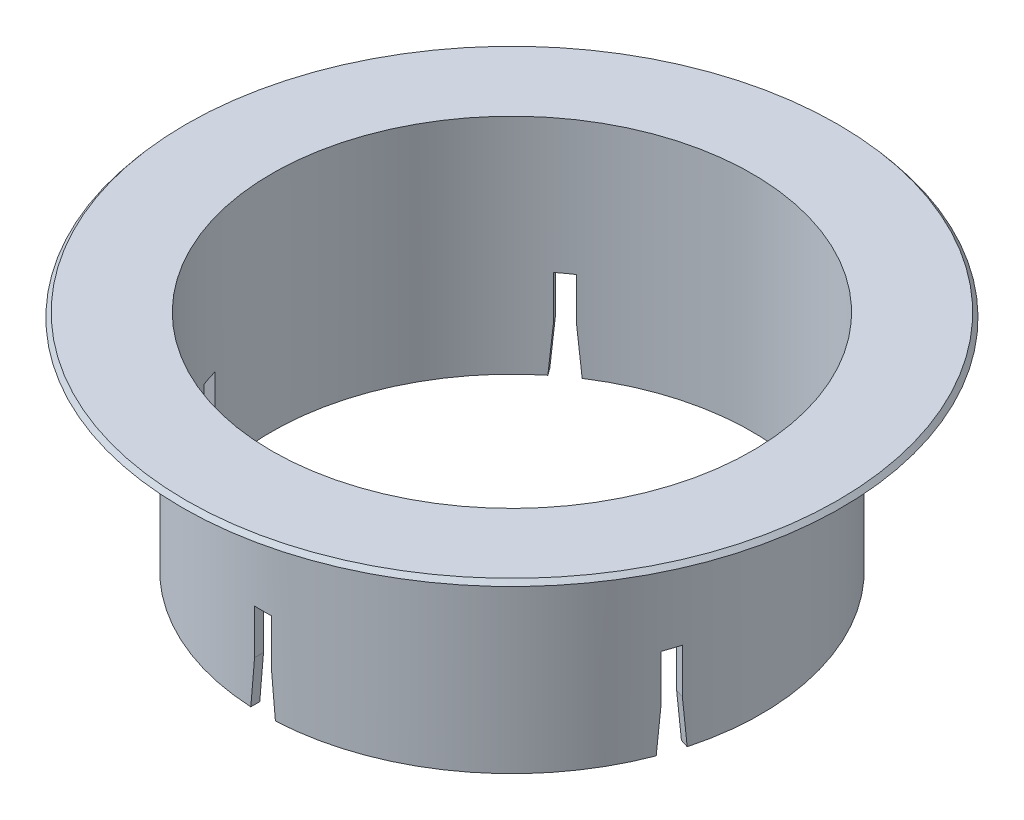
SolidWorks part; units mm, degrees
ref_plane "Front" through (0, 0, 0) normal (0, 0, 1) x (1, 0, 0)
ref_plane "Top" through (0, 0, 0) normal (0, 1, 0) x (1, 0, 0)
ref_plane "Right" through (0, 0, 0) normal (1, 0, 0) x (0, 0, -1)
ref_axis "Axis1" through (-84.4107, 0, 0) along (1, 0, 0)
ref_axis "Axis2" through (0, 64.3378, 0) along (0, -1, 0)
ref_axis "Axis3" through (0, 0, -102.329) along (0, 0, 1)
sketch "Sketch1" plane through (0, 0, 0) normal (1, 0, 0) x (0, 0, -1)
  line L0 (21.5, -20) -> (21.5, 0)
  line L1 (21.5, 0) -> (29.1644, 0)
  line L2 (29.1644, 0) -> (29.5, -0.4)
  line L3 (29.5, -0.4) -> (26.1, -1.4)
  line L4 (26.1, -1.4) -> (26.1, -0.4)
  line L5 (26.1, -0.4) -> (22.3, -0.4)
  line L6 (22.3, -0.4) -> (22.3, -20)
  line L7 (22.3, -20) -> (21.5, -20)
  line L8 (0, 50) -> (0, -50) construction
  dimension "D1" = 3.8
  dimension "D2" = 1
  dimension "D3" = 0.4
  dimension "D4" = 40
  dimension "D5" = 22.3
  dimension "D6" = 0.8
  dimension "D7" = 29.5
  dimension "D8" = 19.6
revolve "Revolve1" add sketch "Sketch1" angle 360 about axis through (0, 64.3378, 0) along (0, -1, 0)
sketch "Sketch2" plane through (0, -20, 0) normal (0, -1, 0) x (1, 0, 0)
  line L1 (-0.75, 22.3) -> (0.75, 22.3)
  line L2 (-0.75, 22.3) -> (-0.75, 21.4869)
  line L3 (-0.75, 21.4869) -> (0.75, 21.4869)
  line L4 (0.75, 22.3) -> (0.75, 21.4869)
  circle A0 centre (0, 0) radius 21.5 construction
  circle A1 centre (0, 0) radius 22.3 construction
  point P4 (0, 21.4869)
  point P9 (0, 22.3)
  dimension "D1" = 1.5
extrude "Cut-Extrude1" cut sketch "Sketch2" against normal blind 8
chamfer "Chamfer1" distance 4 angle 5 2 edges at (-0.75, -20, 21.8871) (0.75, -20, 21.8871) first distance on face at (-0.75, -16, 21.8871) first distance on face at (0.75, -16, 21.8871)
pattern_circular "CirPattern1" count 5 over 360 about axis through (0, 64.3378, 0) along (0, -1, 0) of "Chamfer1", "Cut-Extrude1"
